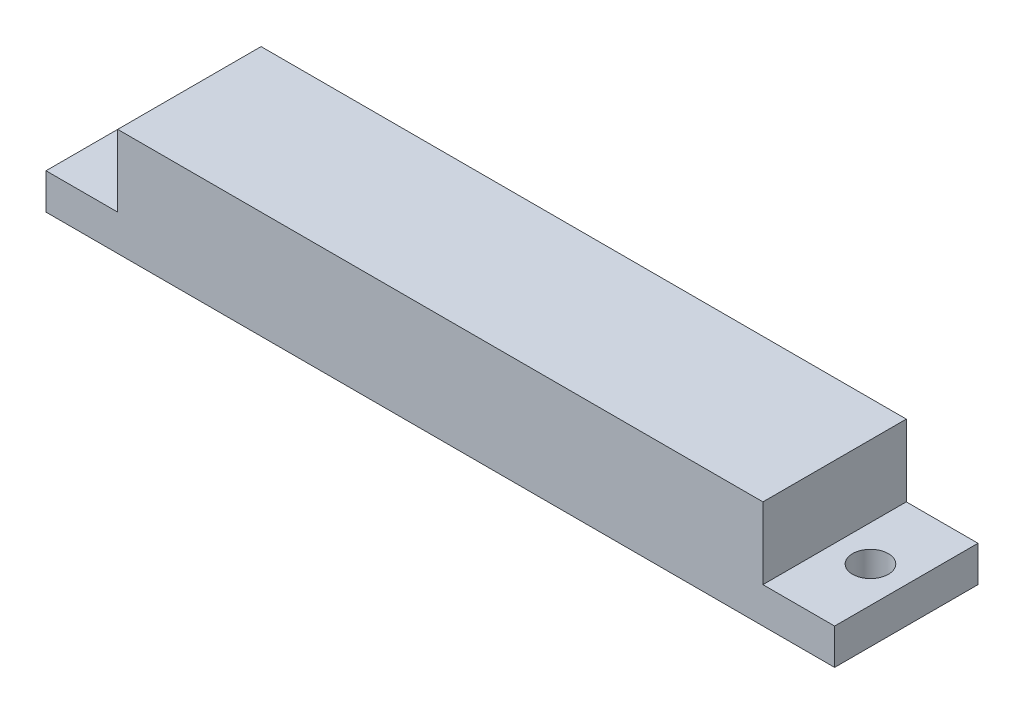
SolidWorks part; units mm, degrees
ref_plane "Front Plane" through (0, 0, 0) normal (0, 0, 1) x (1, 0, 0)
ref_plane "Top Plane" through (0, 0, 0) normal (0, 1, 0) x (1, 0, 0)
ref_plane "Right Plane" through (0, 0, 0) normal (1, 0, 0) x (0, 0, -1)
sketch "Sketch2" plane through (0, 0, 0) normal (0, 0, 1) x (1, 0, 0)
  line L0 (0, 0) -> (0, 7.9375) construction
  line L1 (-34.925, 1.5875) -> (-28.575, 1.5875)
  line L2 (-34.925, 1.5875) -> (-34.925, -1.5875)
  line L3 (-34.925, -1.5875) -> (34.925, -1.5875)
  line L4 (34.925, 1.5875) -> (34.925, -1.5875)
  line L5 (-34.925, 1.5875) -> (34.925, -1.5875) construction
  line L6 (-34.925, -1.5875) -> (34.925, 1.5875) construction
  line L7 (-28.575, 1.5875) -> (-28.575, 7.9375)
  line L8 (-28.575, 7.9375) -> (28.575, 7.9375)
  line L9 (28.575, 1.5875) -> (28.575, 7.9375)
  line L10 (28.575, 1.5875) -> (34.925, 1.5875)
  point P0 (0, 0)
  point P10 (0, 0)
  dimension "D1" = 69.85
  dimension "D2" = 3.175
  dimension "D3" = 6.35
  dimension "D4" = 6.35
extrude "Boss-Extrude1" add sketch "Sketch2" against normal mid plane 12.7
sketch "Sketch6" plane through (0, 1.5875, 0) normal (0, 1, 0) x (1, 0, 0)
  line L0 (-34.925, 0) -> (34.925, 0) construction
  line L1 (-34.925, 6.35) -> (-34.925, -6.35) construction
  line L2 (34.925, 6.35) -> (34.925, -6.35) construction
  line L3 (0, 0) -> (0, 11.5563) construction
  circle A0 centre (-31.75, 0) radius 1.5875
  circle A1 centre (31.75, 0) radius 1.5875
  dimension "D1" = 3.175
  dimension "D2" = 3.175
extrude "Cut-Extrude1" cut sketch "Sketch6" against normal through all
